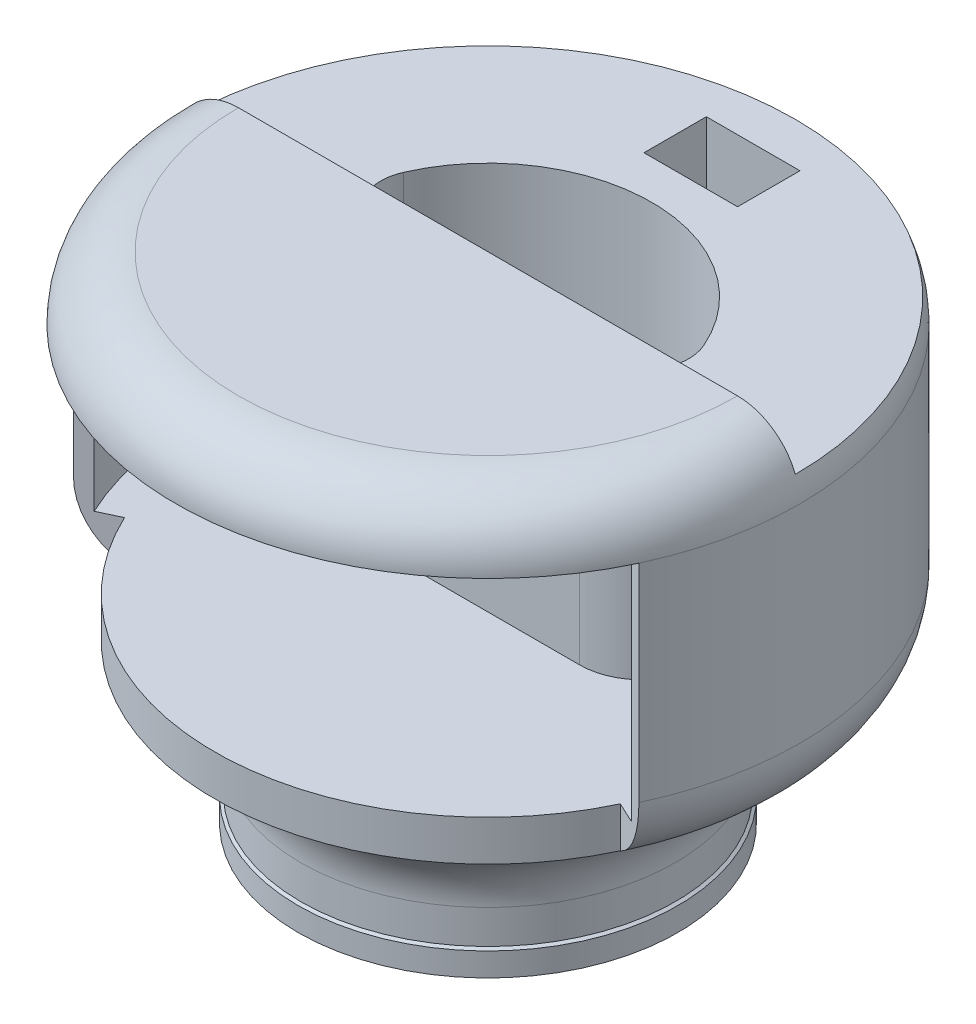
SolidWorks part; units mm, degrees
ref_plane "Front Plane" through (0, 0, 0) normal (0, 0, 1) x (1, 0, 0)
ref_plane "Top Plane" through (0, 0, 0) normal (0, 1, 0) x (1, 0, 0)
ref_plane "Right Plane" through (0, 0, 0) normal (1, 0, 0) x (0, 0, -1)
sketch "Sketch1" plane through (0, 0, 0) normal (0, 0, 1) x (1, 0, 0)
  line L0 (0, 0) -> (0, 90.2242) construction
  line L28 (0, 63.4279) -> (32, 63.4279)
  line L29 (40, 55.4279) -> (40, 28.8468)
  line L30 (22.5, 0) -> (24.35, 0)
  line L31 (24.35, 0) -> (24.35, 3)
  line L32 (24.35, 3) -> (24, 3.25)
  line L33 (24, 3.25) -> (24, 7.5811)
  line L34 (28.5399, 15.9588) -> (35.4601, 20.4691)
  line L35 (0, 13) -> (22, 13)
  line L36 (22.5, 12.5) -> (22.5, 0)
  line L37 (0, 13) -> (0, 63.4279)
  arc A0 (22, 13) -> (22.5, 12.5) centre (22, 12.5) cw
  arc A1 (24, 7.5811) -> (28.5399, 15.9588) centre (34, 7.5811) cw
  arc A2 (35.4601, 20.4691) -> (40, 28.8468) centre (30, 28.8468) ccw
  arc A3 (32, 63.4279) -> (40, 55.4279) centre (32, 55.4279) cw
  point P11 (22.9, 63.4279)
  point P18 (22.5, 13)
  point P21 (24, 13)
  point P24 (40, 23.4279)
  point P27 (40, 63.4279)
  point P28 (28.5604, 23.4279)
  point P31 (22.5, 17)
  dimension "D8" = 9.75
  dimension "D9" = 0.5
  dimension "D4" = 1.85
  dimension "D1" = 22.5
  dimension "D10" = 10
  dimension "D11" = 10
  dimension "D12" = 8
  dimension "D2" = 40
  dimension "D3" = 40
  dimension "D5" = 1.5
  dimension "D6" = 3
  dimension "D7" = 13
revolve "Revolve1" add sketch "Sketch1" angle 360 about L0
ref_plane "Plane1" through (0, 13, 0) normal (0, -1, 0) x (-1, 0, 0)
sketch "Sketch18" plane through (0, 0, 0) normal (0, 0, 1) x (1, 0, 0)
  line L0 (0, 0) -> (0, 101.5813) construction
  line L1 (-24.35, 0) -> (24.35, 0) construction
sketch "Sketch3" plane through (0, 0, 0) normal (0, 0, 1) x (1, 0, 0)
  point P0 (1.2404, 19.1989)
ref_point "Point1"
ref_plane "Plane2" through (0, 0, 22.9) normal (0, 0, 1) x (1, 0, 0)
ref_plane "Plane3" through (0, 0, 40) normal (0, 0, 1) x (1, 0, 0)
ref_plane "Plane4" through (0, 55.4279, 0) normal (0, 1, 0) x (1, 0, 0)
sketch "Sketch9" plane through (0, 55.4279, 0) normal (0, 1, 0) x (1, 0, 0)
  circle A7 centre (0, 0) radius 38
  circle A8 centre (0, 0) radius 40 construction
  circle A9 centre (0, 0) radius 23
  dimension "D1" = 2
  dimension "D2" = 46
ref_plane "Plane5" through (0, 13, 0) normal (0, -1, 0) x (-1, 0, 0)
sketch "Sketch11" plane through (0, 13, 0) normal (0, -1, 0) x (-1, 0, 0)
  line L0 (-21, 0) -> (21, 0)
  arc A1 (-21, 0) -> (21, 0) centre (0, 0) cw
  dimension "D1" = 42
extrude "Cut-Extrude3" cut sketch "Sketch11" against normal blind 60
ref_plane "Plane6" through (0, 0, -40) normal (0, 0, -1) x (-1, 0, 0)
extrude "Cut-Extrude5" cut sketch "Sketch9" against normal blind 30 and the other way blind 2
sketch "Sketch19" plane through (0, 0, 0) normal (1, 0, 0) x (0, 0, -1)
  line L0 (-47.0647, 55.4279) -> (-35.0647, 55.4279)
  line L1 (31.2976, 55.4279) -> (-31.2976, 55.4279) construction
  line L2 (-35.0647, 55.4279) -> (-35.0647, 18.9279)
  line L3 (-35.0647, 18.9279) -> (-47.0647, 18.9279)
  line L4 (-47.0647, 18.9279) -> (-47.0647, 55.4279)
  dimension "D1" = 12
  dimension "D2" = 36.5
revolve "Cut-Revolve2" cut sketch "Sketch19" angle 65 about L0 other way angle 65
ref_plane "Plane7" through (0, 0, 22.5) normal (0, 0, -1) x (-1, 0, 0)
sketch "Sketch21" plane through (0, 0, 22.5) normal (0, 0, -1) x (-1, 0, 0)
  line L0 (0, 0) -> (0, 101.5813) construction
  line L1 (-1.625, 4) -> (1.625, 4)
  line L2 (-1.625, 4) -> (-1.625, 0)
  line L3 (-1.625, 0) -> (1.625, 0)
  line L4 (1.625, 4) -> (1.625, 0)
  line L5 (-1.625, 4) -> (1.625, 0) construction
  line L6 (-1.625, 0) -> (1.625, 4) construction
  line L7 (-22.5, 0) -> (22.5, 0) construction
  point P0 (0, 2)
  dimension "D1" = 4
  dimension "D2" = 3.25
extrude "Boss-Extrude3" add sketch "Sketch21" along normal blind 1.35
pattern_circular "CirPattern1" count 5 over 360 about axis through (0, 0, 0) along (0, -1, 0) of "Boss-Extrude3"
ref_plane "Plane8" through (0, 20.4691, 0) normal (0, 1, 0) x (1, 0, 0)
sketch "Sketch22" plane through (0, 63.4279, 0) normal (0, 1, 0) x (1, 0, 0)
  line L0 (-40, 0) -> (40, 0)
  arc A0 (-40, 0) -> (40, 0) centre (0, 0) cw
  arc A1 (36.2523, -16.9047) -> (-36.2523, -16.9047) centre (0, 0) ccw construction
extrude "Cut-Extrude9" cut sketch "Sketch22" against normal blind 5
sketch "Sketch23" plane through (0, 0, -40) normal (0, 0, -1) x (-1, 0, 0)
  line L0 (0, 0) -> (0, 101.5813) construction
  line L1 (31.2976, 55.4279) -> (-31.2976, 55.4279) construction
  circle A0 centre (0, 42.1379) radius 10.5
  dimension "D1" = 21
  dimension "D2" = 13.29
extrude "Cut-Extrude10" cut sketch "Sketch23" against normal blind 10
sketch "Sketch24" plane through (0, 58.4279, 0) normal (0, 1, 0) x (1, 0, 0)
  line L1 (-8.5, 36) -> (8.5, 36)
  line L2 (-8.5, 36) -> (-8.5, 24)
  line L3 (-8.5, 24) -> (8.5, 24)
  line L4 (8.5, 36) -> (8.5, 24)
  line L5 (-8.5, 36) -> (8.5, 24) construction
  line L6 (-8.5, 24) -> (8.5, 36) construction
  arc A0 (39.4162, 0) -> (-39.4162, 0) centre (0, 0) ccw construction
  point P0 (0, 30)
  dimension "D1" = 30
  dimension "D2" = 12
  dimension "D3" = 17
extrude "Boss-Extrude4" add sketch "Sketch24" against normal blind 8
sketch "Sketch26" plane through (0, 58.4279, 0) normal (0, 1, 0) x (1, 0, 0)
  line L1 (-6, 34) -> (6, 34)
  line L2 (-6, 34) -> (-6, 26)
  line L3 (-6, 26) -> (6, 26)
  line L4 (6, 34) -> (6, 26)
  line L5 (-6, 34) -> (6, 26) construction
  line L6 (-6, 26) -> (6, 34) construction
  arc A0 (39.4162, 0) -> (-39.4162, 0) centre (0, 0) ccw construction
  point P0 (0, 30)
  dimension "D1" = 30
  dimension "D2" = 8
  dimension "D3" = 12
extrude "Cut-Extrude11" cut sketch "Sketch26" against normal blind 10
sketch "Sketch27" plane through (8.5, 0, 0) normal (1, 0, 0) x (0, 0, -1)
  line L0 (36, 50.4279) -> (36, 57.4279) construction
  line L1 (28, 56.4279) -> (32, 56.4279)
  line L2 (28, 56.4279) -> (28, 51.4279)
  line L3 (28, 51.4279) -> (32, 51.4279)
  line L4 (32, 56.4279) -> (32, 51.4279)
  line L5 (28, 56.4279) -> (32, 51.4279) construction
  line L6 (28, 51.4279) -> (32, 56.4279) construction
  line L7 (24, 50.4279) -> (24, 57.4279) construction
  line L8 (24, 50.4279) -> (36, 50.4279) construction
  point P0 (30, 53.9279)
  dimension "D1" = 12
  dimension "D2" = 3.5
  dimension "D3" = 5
  dimension "D4" = 4
extrude "Cut-Extrude12" cut sketch "Sketch27" against normal blind 5
ref_plane "Plane9" through (-39.4162, 58.4279, 0) normal (0.375, 0.927, 0) x (0.927, -0.375, 0)
ref_plane "Plane10" through (0, 58.4279, 0) normal (0, 1, 0) x (1, 0, 0)
sketch "Sketch28" plane through (0, 55.4279, 0) normal (0, 1, 0) x (1, 0, 0)
  line L0 (-22.9129, -2) -> (22.9129, -2)
  arc A0 (-22.9129, -2) -> (22.9129, -2) centre (0, 0) ccw
  dimension "D1" = 46
  dimension "D2" = 2
extrude "Cut-Extrude14" cut sketch "Sketch28" against normal blind 30 and the other way blind 2
sketch "Sketch29" plane through (0, 0, 0) normal (0, 0, -1) x (-1, 0, 0)
  line L0 (0, 0) -> (0, 101.5813) construction
  line L1 (32, 63.4279) -> (-32, 63.4279) construction
  circle A0 centre (-30.4162, 60.9279) radius 1
  circle A1 centre (30.4162, 60.9279) radius 1
  circle A2 centre (0, 60.9279) radius 1
  dimension "D1" = 2
  dimension "D2" = 2
  dimension "D3" = 2
  dimension "D4" = 2.5
  dimension "D5" = 2.5
  dimension "D6" = 2.5
  dimension "D7" = 9
  dimension "D8" = 9
extrude "Cut-Extrude15" cut sketch "Sketch29" against normal blind 15
fillet "Fillet1" radius 6 2 edges at (-21, 35.7139, 0) (21, 35.7139, 0)
fillet "Fillet2" radius 8 2 edges at (22.9129, 41.4279, 2) (-22.9129, 41.4279, 2)
